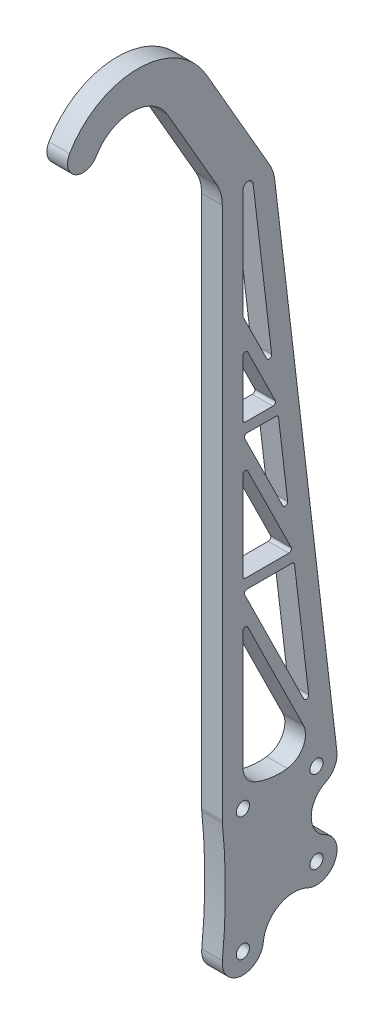
SolidWorks part; units mm, degrees
ref_plane "Front Plane" through (0, 0, 0) normal (0, 0, 1) x (1, 0, 0)
ref_plane "Top Plane" through (0, 0, 0) normal (0, 1, 0) x (1, 0, 0)
ref_plane "Right Plane" through (0, 0, 0) normal (1, 0, 0) x (0, 0, -1)
sketch "Sketch1" plane through (0, 0, 0) normal (1, 0, 0) x (0, 0, -1)
  line L1 (11.35, 19.05) -> (11.35, -6.35) construction
  line L2 (-11.35, -19.05) -> (-11.35, 19.05) construction
  line L3 (11.35, 0) -> (-11.35, 0) construction
  line L4 (-6.35, 19.05) -> (6.35, 19.05) construction
  line L5 (-17.7, 19.05) -> (-17.7, 183.3563)
  line L6 (8.5879, -12.0678) -> (-3.6653, -6.1486) construction
  line L7 (17.6561, 19.7951) -> (-1.825, 184.6629)
  line L8 (-11.35, 25.4) -> (-11.35, 69.85)
  line L9 (-56.5215, 215.9) -> (-71.6445, 189.7062) construction
  line L10 (-60.6459, 170.6563) -> (-30.4, 170.6563) construction
  line L11 (-19.4015, 189.7062) -> (-34.5244, 215.9)
  line L12 (-45.523, 209.55) -> (-60.6459, 183.3562) construction
  line L13 (-60.6459, 183.3562) -> (-30.4, 183.3562) construction
  line L14 (-30.4, 183.3562) -> (-45.523, 209.55) construction
  line L15 (-22.6094, 220.6625) -> (-1.825, 184.6629)
  line L16 (-1.825, 184.6629) -> (-12.8235, 178.3129) construction
  line L17 (-56.5215, 215.9) -> (-64.7704, 220.6625) construction
  line L18 (14.1121, -0.6322) -> (6.2486, 3.1664) construction
  line L19 (-11.35, 69.85) -> (10.6049, 25.3561)
  line L20 (10.6049, 25.3561) -> (-0.8043, 121.9108) construction
  line L21 (8.5879, 24.7678) -> (0.6662, 20.9411) construction
  line L22 (14.1121, 13.3322) -> (6.5563, 9.6822) construction
  line L23 (9.4901, 34.7905) -> (-11.35, 77.0252)
  line L24 (-11.35, 77.0252) -> (4.4995, 77.0252)
  line L25 (4.4995, 77.0252) -> (9.4901, 34.7905)
  line L26 (4.1244, 80.2002) -> (-11.35, 80.2002)
  line L27 (-11.35, 80.2002) -> (-11.35, 111.5606)
  line L28 (-11.35, 111.5606) -> (4.1244, 80.2002)
  line L29 (3.0096, 89.6346) -> (-11.35, 118.7358)
  line L30 (-11.35, 118.7358) -> (-0.4291, 118.7358)
  line L31 (-0.4291, 118.7358) -> (3.0096, 89.6346)
  line L32 (-0.8043, 121.9108) -> (-11.35, 121.9108)
  line L33 (-11.35, 121.9108) -> (-11.35, 143.2829)
  line L34 (-8.186, 184.3819) -> (-1.919, 131.3452)
  line L35 (-11.35, 69.85) -> (-8.5028, 71.2549) construction
  line L36 (-11.35, 77.0252) -> (-11.35, 80.2002) construction
  line L37 (-11.35, 111.5606) -> (-8.5028, 112.9656) construction
  line L38 (-11.35, 118.7358) -> (-11.35, 121.9108) construction
  line L39 (-0.8043, 121.9108) -> (-11.35, 143.2829)
  line L40 (-1.919, 131.3452) -> (-11.35, 150.4581)
  line L41 (-11.35, 143.2829) -> (-8.5028, 144.6878) construction
  line L42 (-1.919, 131.3452) -> (-1.3257, 126.3235) construction
  line L43 (-11.35, 150.4581) -> (-11.35, 184.1956)
  line L44 (-17.6679, -18.4122) -> (-15.1883, 6.15) construction
  line L45 (-5.0321, -19.6878) -> (-3.6653, -6.1486) construction
  circle A0 centre (-11.35, 19.05) radius 5 construction
  circle A1 centre (11.35, 19.05) radius 5 construction
  arc A2 (-17.6679, -18.4122) -> (-5.0321, -19.6878) centre (-11.35, -19.05) ccw
  arc A3 (8.5879, -12.0678) -> (14.1121, -0.6322) centre (11.35, -6.35) ccw
  arc A4 (14.1121, 13.3322) -> (17.6561, 19.7951) centre (11.35, 19.05) ccw
  arc A5 (14.1121, 13.3322) -> (14.1121, -0.6322) centre (17.485, 6.35) ccw
  arc A7 (-34.5244, 215.9) -> (-56.5215, 215.9) centre (-45.523, 209.55) ccw
  arc A8 (-71.6445, 189.7062) -> (-60.6459, 170.6563) centre (-60.6459, 183.3562) ccw construction
  arc A9 (-30.4, 170.6563) -> (-19.4015, 189.7062) centre (-30.4, 183.3562) ccw construction
  circle A10 centre (-45.523, 192.0875) radius 8.7312 construction
  arc A11 (-17.7, 183.3563) -> (-19.4015, 189.7062) centre (-30.4, 183.3563) ccw
  arc A12 (-56.5215, 215.9) -> (-64.7704, 220.6625) centre (-60.6459, 218.2813) cw
  arc A13 (-64.7704, 220.6625) -> (-22.6094, 220.6625) centre (-43.6899, 208.4917) cw
  arc A14 (-5.0321, -19.6878) -> (8.5879, -12.0678) centre (4.4447, -20.6445) cw
  arc A15 (-11.35, 25.4) -> (-8.5879, 24.7678) centre (-11.35, 19.05) cw
  arc A17 (10.6049, 25.3561) -> (8.5879, 24.7678) centre (11.35, 19.05) ccw
  arc A18 (8.5879, 24.7678) -> (-8.5879, 24.7678) centre (0, 42.5454) cw
  arc A19 (-11.35, 184.1956) -> (-8.186, 184.3819) centre (-9.7625, 184.1956) cw
  arc A20 (-17.7, 19.05) -> (-17.6679, 18.4122) centre (-11.35, 19.05) ccw
  arc A21 (-17.6679, -18.4122) -> (-17.6679, 18.4122) centre (-200.0545, 0) ccw
  point P11 (0, 0)
  point P47 (-11.35, 0)
  point P48 (-45.523, 222.25)
  point P73 (-5.8633, -8.479)
  point P77 (-10.2526, 2.2127)
  point P78 (-1.3257, -9.1781)
  point P79 (-2.8798, -7.5527)
  point P80 (-1.919, -8.4753)
  point P82 (0, -12.6969)
  point P83 (-13.498, 6.35)
  point P84 (-17.9074, 21.0908)
  dimension "D3" = 12.7
  dimension "D4" = 10
  dimension "D5" = 6.35
  dimension "D6" = 15.875
  dimension "D7" = 12.7
  dimension "D9" = 12.7
  dimension "D10" = 4.7625
  dimension "D12" = 6.35
  dimension "D14" = 3.175
  dimension "D15" = 1.5875
  dimension "D17" = 9.525
  dimension "D1" = 25.4
  dimension "D2" = 38.1
  dimension "D8" = 38.8937
  dimension "D11" = 222.25
  dimension "D13" = 6.35
  dimension "D16" = 44.45
extrude "Boss-Extrude1" add sketch "Sketch1" along normal mid plane 6.35
sketch "Sketch2" plane through (3.175, 0, 0) normal (1, 0, 0) x (0, 0, -1)
  line L0 (-11.35, -19.05) -> (-11.35, 19.05) construction
  circle A0 centre (11.35, -6.35) radius 2.032
  circle A1 centre (11.35, 19.05) radius 2.032
  circle A2 centre (-11.35, 19.05) radius 2.032
  circle A3 centre (-11.35, -19.05) radius 2.032
  point P11 (0, 0)
  point P12 (-11.35, 23.0978)
  point P13 (0, 0)
  dimension "D1" = 4.064
extrude "Cut-Extrude1" cut sketch "Sketch2" against normal through all
fillet "Fillet1" radius 12.7 1 edges at (0, 184.6629, 1.825)
fillet "Fillet2" radius 0.7937 15 edges at (0, 121.9108, 11.35) (0, 118.7358, 11.35) (0, 118.7358, 0.4291) (0, 89.6346, -3.0096) (0, 111.5606, 11.35) (0, 80.2002, 11.35) (0, 80.2002, -4.1244) (0, 69.85, 11.35) (0, 77.0252, 11.35) (0, 77.0252, -4.4995) (0, 34.7905, -9.4901) (0, 150.4581, 11.35) (0, 121.9108, 0.8043) (0, 143.2829, 11.35) (0, 131.3452, 1.919)
fillet "Fillet3" radius 6.35 2 edges at (0, 25.4, 11.35) (0, 25.3561, -10.6049)
